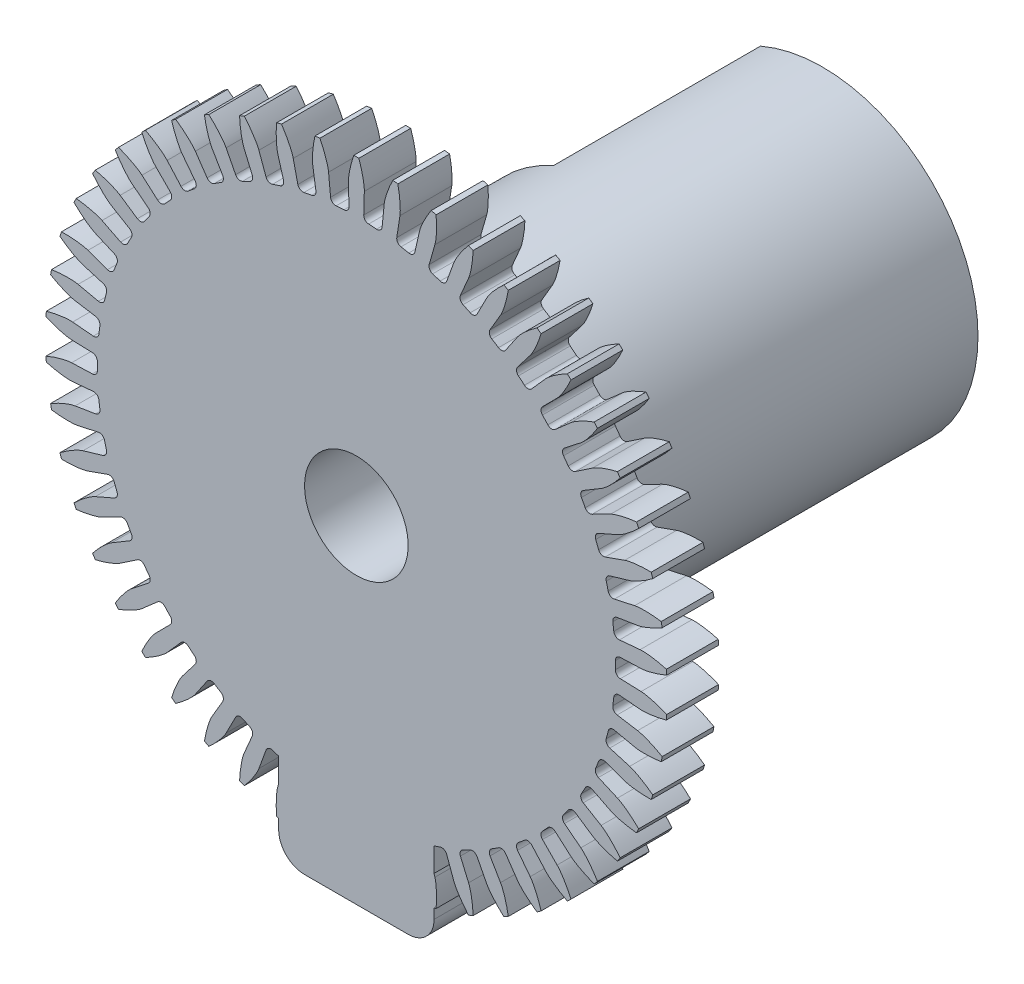
SolidWorks part; units mm, degrees
ref_plane "Piano frontale" through (0, 0, 0) normal (0, 0, 1) x (1, 0, 0)
ref_plane "Piano superiore" through (0, 0, 0) normal (0, 1, 0) x (1, 0, 0)
ref_plane "Piano destro" through (0, 0, 0) normal (1, 0, 0) x (0, 0, -1)
sketch "Schizzo1" plane through (0, 0, 0) normal (0, 0, 1) x (1, 0, 0)
  circle A0 centre (0, 0) radius 6
  circle A2 centre (0, 0) radius 1
  dimension "D1" = 2
  dimension "D2" = 12
extrude "Estrusione-Estrusione1" add sketch "Schizzo1" along normal blind 1
sketch "Schizzo2" plane through (0, 0, 1) normal (0, 0, 1) x (1, 0, 0)
  line L0 (0, 0) -> (6, 0) construction
  line L7 (6, 0) -> (0, 0) construction
  line L8 (0, 0) -> (5.4966, 0.1919) construction
  line L9 (0, 0) -> (5.4966, -0.1919) construction
  line L10 (8.3142, -2.6251) -> (8.3142, 2.6251)
  line L11 (5.4966, -0.1919) -> (5.0959, -0.178)
  line L12 (5.4966, 0.1919) -> (5.0959, 0.178)
  circle A1 centre (0, 0) radius 6 construction
  arc A7 (5.4966, -0.1919) -> (5.4966, 0.1919) centre (0, 0) ccw construction
  arc A8 (4.9994, -0.0765) -> (4.9994, 0.0765) centre (0, 0) ccw
  arc A9 (4.9994, 0.0765) -> (5.0959, 0.178) centre (5.0994, 0.078) cw
  arc A10 (4.9994, -0.0765) -> (5.0959, -0.178) centre (5.0994, -0.078) ccw
  spline S0 degree 4 poles (5.4966, 0.1919) (5.5023, 0.1921) (5.5182, 0.1931) (5.5482, 0.1964) (5.5968, 0.204) (5.6583, 0.2168) (5.737, 0.2371) (5.8288, 0.2655) (5.9283, 0.3015) (6.0349, 0.3457) (6.1398, 0.3943) (6.2427, 0.4469) (6.3438, 0.5029) (6.4642, 0.5749) (6.6058, 0.667) (6.7668, 0.783) (6.9438, 0.9241) (7.1177, 1.0777) (7.2834, 1.2368) (7.444, 1.4063) (7.5946, 1.5765) (7.7436, 1.7616) (7.8773, 1.9368) (8.0184, 2.1419) (8.1298, 2.3099) (8.2671, 2.5404) (8.3452, 2.679) (8.4332, 2.8442) (8.4704, 2.919) (8.4934, 2.9651) knots 0 0 0 0 0 0.005377 0.015084 0.028532 0.04661 0.064855 0.092111 0.119476 0.146842 0.174209 0.201575 0.228941 0.256307 0.307035 0.361767 0.4165 0.471232 0.525964 0.580697 0.635429 0.690161 0.744894 0.799626 0.854358 0.909091 0.954545 1 1 1 1 1 construction
  spline S1 degree 4 poles (5.4966, 0.1919) (5.5023, 0.1921) (5.5182, 0.1931) (5.5482, 0.1964) (5.5968, 0.204) (5.6583, 0.2168) (5.737, 0.2371) (5.8288, 0.2655) (5.9283, 0.3015) (6.0349, 0.3457) (6.1398, 0.3943) (6.2427, 0.4469) (6.3438, 0.5029) (6.4642, 0.5749) (6.6058, 0.667) (6.7668, 0.783) (6.9438, 0.9241) (7.1177, 1.0777) (7.2834, 1.2368) (7.444, 1.4063) (7.5946, 1.5765) (7.7436, 1.7616) (7.8773, 1.9368) (8.0184, 2.1419) (8.1298, 2.3099) (8.2373, 2.4904) (8.2885, 2.5792) (8.3142, 2.6251) knots 0 0 0 0 0 0.005377 0.015084 0.028532 0.04661 0.064855 0.092111 0.119476 0.146842 0.174209 0.201575 0.228941 0.256307 0.307035 0.361767 0.4165 0.471232 0.525964 0.580697 0.635429 0.690161 0.744894 0.799626 0.854358 0.909091 0.909091 0.909091 0.909091 0.909091
  spline S2 degree 4 poles (5.4966, -0.1919) (5.5023, -0.1921) (5.5182, -0.1931) (5.5482, -0.1964) (5.5968, -0.204) (5.6583, -0.2168) (5.737, -0.2371) (5.8288, -0.2655) (5.9283, -0.3015) (6.0349, -0.3457) (6.1398, -0.3943) (6.2427, -0.4469) (6.3438, -0.5029) (6.4642, -0.5749) (6.6058, -0.667) (6.7668, -0.783) (6.9438, -0.9241) (7.1177, -1.0777) (7.2834, -1.2368) (7.444, -1.4063) (7.5946, -1.5765) (7.7436, -1.7616) (7.8773, -1.9368) (8.0184, -2.1419) (8.1298, -2.3099) (8.2373, -2.4904) (8.2885, -2.5792) (8.3142, -2.6251) knots 0 0 0 0 0 0.005377 0.015084 0.028532 0.04661 0.064855 0.092111 0.119476 0.146842 0.174209 0.201575 0.228941 0.256307 0.307035 0.361767 0.4165 0.471232 0.525964 0.580697 0.635429 0.690161 0.744894 0.799626 0.854358 0.909091 0.909091 0.909091 0.909091 0.909091
  point P5 (4.997, 0.1745)
  point P17 (4.997, -0.1745)
  dimension "D3" = 2
  dimension "D1" = 11
  dimension "D4" = 2
  dimension "D5" = 0.1
  dimension "D2" = 10
  dimension "D6" = 0.1
extrude "Taglio-Estrusione1" cut sketch "Schizzo2" against normal up to next
pattern_circular "RipetizioneCircolare1" count 50 over 360 about axis through (0, 0, 1) along (0, 0, 1) of "Taglio-Estrusione1"
sketch "Schizzo3" plane through (0, 0, 0) normal (0, 0, -1) x (-1, 0, 0)
  circle A0 centre (0, 0) radius 1 construction
  circle A1 centre (0, 0) radius 1
  circle A2 centre (0, 0) radius 3
  dimension "D1" = 6
extrude "Estrusione-Estrusione2" add sketch "Schizzo3" along normal blind 8
sketch "Schizzo4" plane through (0, 0, 0) normal (0, 0, -1) x (-1, 0, 0)
  line L1 (-1, -6.4998) -> (1, -6.4998)
  line L2 (-1.5, -5.9998) -> (-1.5, -4.4998)
  line L3 (-1.5, -4.4998) -> (1.5, -4.4998)
  line L4 (1.5, -5.9998) -> (1.5, -4.4998)
  arc A0 (-1.5, -5.9998) -> (-1, -6.4998) centre (-1, -5.9998) ccw
  arc A1 (1.5, -5.9998) -> (1, -6.4998) centre (1, -5.9998) cw
  point P5 (0, -4.4998)
  point P7 (0, 0)
  point P11 (-1.5, -6.4998)
  point P14 (1.5, -6.4998)
  dimension "D4" = 0.5
  dimension "D5" = 0.5
  dimension "D1" = 0.5
  dimension "D2" = 2
  dimension "D3" = 3
extrude "Estrusione-Estrusione3" add sketch "Schizzo4" along normal blind 2.5 from surface starting at face at (0, 0, 1)
sketch "Schizzo5" plane through (0, 0, -8) normal (0, 0, -1) x (-1, 0, 0)
  line L0 (1.2, 2.7495) -> (1.2, -2.7495)
  circle A0 centre (0, 0) radius 1 construction
  circle A1 centre (0, 0) radius 3
  arc A2 (1.2, -2.7495) -> (1.2, 2.7495) centre (0, 0) ccw
  point P8 (1.2, 0)
  dimension "D2" = 1.2
  dimension "D1" = 0
extrude "Taglio-Estrusione2" cut sketch "Schizzo5" against normal blind 4
sketch "Schizzo6" plane through (0, 0, 1) normal (0, 0, 1) x (1, 0, 0)
  circle A0 centre (0, 0) radius 1 construction
  circle A1 centre (0, 0) radius 1
extrude "Estrusione-Estrusione4" add sketch "Schizzo6" along normal blind 1 from offset 4 offset against normal yes
